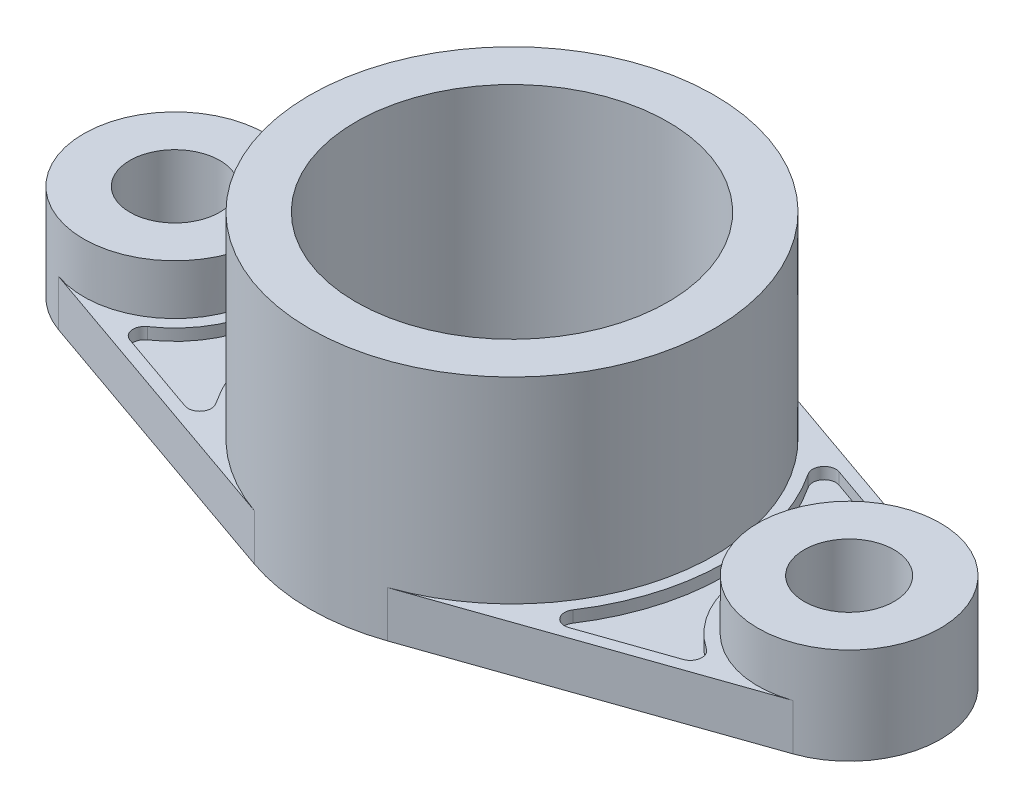
SolidWorks part; units mm, degrees
ref_plane "Front Plane" through (0, 0, 0) normal (0, 0, 1) x (1, 0, 0)
ref_plane "Top Plane" through (0, 0, 0) normal (0, 1, 0) x (1, 0, 0)
ref_plane "Right Plane" through (0, 0, 0) normal (1, 0, 0) x (0, 0, -1)
sketch "Sketch1" plane through (0, 0, 0) normal (0, 1, 0) x (1, 0, 0)
  line L0 (-55, 0) -> (55, 0) construction
  line L1 (-95.2986, 22.3431) -> (-17.301, 49.5674)
  line L2 (-95.2986, -22.3431) -> (-17.301, -49.5674)
  line L3 (0, -55) -> (0, 55) construction
  line L4 (95.2986, 22.3431) -> (17.301, 49.5674)
  line L5 (95.2986, -22.3431) -> (17.301, -49.5674)
  circle A0 centre (0, 0) radius 40.5
  circle A1 centre (0, 0) radius 52.5
  circle A2 centre (-87.5, 0) radius 11.665
  circle A3 centre (87.5, 0) radius 11.665
  circle A4 centre (87.5, 0) radius 23.665
  circle A5 centre (-87.5, 0) radius 23.665
  point P16 (-112.7077, -33.5474)
  dimension "D1" = 105
  dimension "D2" = 12
  dimension "D5" = 23.33
  dimension "D6" = 12
  dimension "D7" = 23.33
  dimension "D8" = 12
  dimension "D3" = 175
  dimension "D4" = 87.5
extrude "Boss-Extrude1" add sketch "Sketch1" along normal blind 25 contours A5 A2 | A4 A3 region at (-74.1858, 0, -18.7492) region at (106.2492, 0, -13.3142)
extrude "Boss-Extrude3" add sketch "Sketch1<4>" along normal blind 12 contours A5 L2 A1 L1 | A4 L4 A1 L5 region at (-58.0855, 0, 0) region at (58.0855, 0, 0)
sketch "Sketch1<4>" plane through (0, 0, 0) normal (0, 1, 0) x (1, 0, 0) same geometry as "Sketch1"
extrude "Boss-Extrude4" add sketch "Sketch1<5>" along normal blind 63 contours A1 A0 region at (0, 0, -51.0151)
sketch "Sketch1<5>" plane through (0, 0, 0) normal (0, 1, 0) x (1, 0, 0) same geometry as "Sketch1"
sketch "Sketch3" plane through (0, 12, 0) normal (0, 1, 0) x (1, 0, 0)
  line L0 (-49.826, 35.0373) -> (-71.8093, 27.3643)
  line L1 (-71.8093, -27.3643) -> (-49.826, -35.0373)
  line L2 (-95.2986, -22.3431) -> (-17.301, -49.5674)
  line L3 (-17.301, 49.5674) -> (-95.2986, 22.3431)
  line L4 (-95.2986, -22.3431) -> (-17.301, -49.5674)
  line L5 (-17.301, 49.5674) -> (-95.2986, 22.3431)
  line L6 (-78.3996, -25.064) -> (-40.0101, -38.4635) construction
  line L7 (-40.0101, 38.4635) -> (-78.3996, 25.064) construction
  arc A0 (-72.5075, -22.051) -> (-72.5075, 22.051) centre (-87.5, 0) ccw
  arc A1 (-46.3329, 30.5534) -> (-46.3329, -30.5534) centre (0, 0) ccw
  arc A2 (-95.2986, -22.3431) -> (-95.2986, 22.3431) centre (-87.5, 0) ccw
  arc A3 (-17.301, 49.5674) -> (-17.301, -49.5674) centre (0, 0) ccw
  arc A4 (-95.2986, -22.3431) -> (-95.2986, 22.3431) centre (-87.5, 0) ccw
  arc A5 (-17.301, 49.5674) -> (-17.301, -49.5674) centre (0, 0) ccw
  arc A6 (-78.3996, -25.064) -> (-78.3996, 25.064) centre (-87.5, 0) ccw construction
  arc A7 (-71.8093, -27.3643) -> (-72.5075, -22.051) centre (-70.8207, -24.5319) cw
  arc A8 (-40.0101, 38.4635) -> (-40.0101, -38.4635) centre (0, 0) ccw construction
  arc A9 (-49.826, -35.0373) -> (-46.3329, -30.5534) centre (-48.8374, -32.2049) ccw
  arc A10 (-46.3329, 30.5534) -> (-49.826, 35.0373) centre (-48.8374, 32.2049) ccw
  arc A11 (-72.5075, 22.051) -> (-71.8093, 27.3643) centre (-70.8207, 24.5319) cw
  dimension "D3" = 3
  dimension "D1" = 0
  dimension "D2" = 3
extrude "Cut-Extrude1" cut sketch "Sketch3" against normal blind 3 contours L0 A11 A0 A7 L1 A9 A1 A10
mirror "Mirror1" about plane through (0, 0, 0) normal (1, 0, 0) of "Cut-Extrude1"
